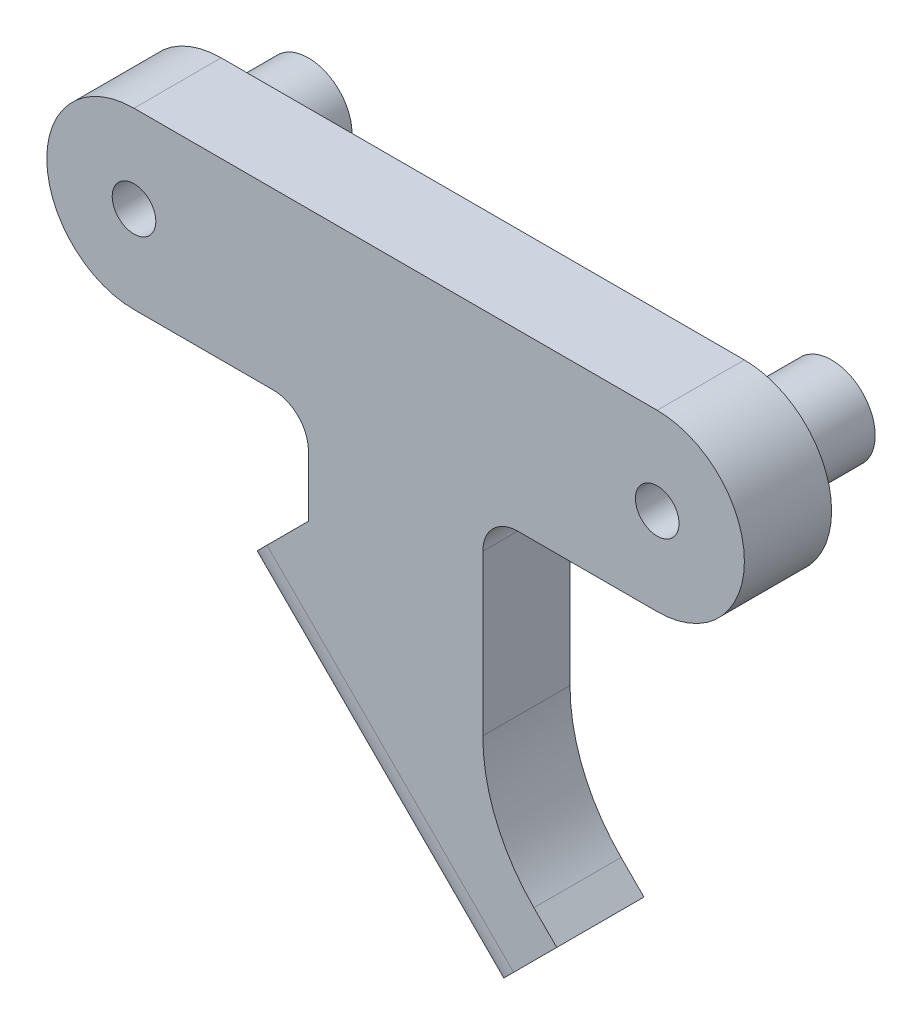
SolidWorks part; units mm, degrees
ref_plane "Piano frontale" through (0, 0, 0) normal (0, 0, 1) x (1, 0, 0)
ref_plane "Piano superiore" through (0, 0, 0) normal (0, 1, 0) x (1, 0, 0)
ref_plane "Piano destro" through (0, 0, 0) normal (1, 0, 0) x (0, 0, -1)
sketch "Schizzo1" plane through (0, 0, 0) normal (0, 0, 1) x (1, 0, 0)
  line L1 (-13.208, 5) -> (16.792, 5)
  line L2 (-13.208, -5) -> (-3.208, -5)
  line L3 (6.792, -28.7941) -> (6.792, -18.7941)
  line L4 (-3.208, -18.7941) -> (6.792, -28.7941)
  line L5 (6.792, -5) -> (16.792, -5)
  line L7 (-3.208, -5) -> (-3.208, -18.7941)
  line L9 (6.792, -5) -> (6.792, -18.7941)
  line L10 (6.792, 0) -> (16.792, 0) construction
  arc A0 (-13.208, 5) -> (-13.208, -5) centre (-13.208, 0) ccw
  arc A1 (16.792, -5) -> (16.792, 5) centre (16.792, 0) ccw
  point P3 (1.792, 0)
  dimension "D1" = 30
  dimension "D2" = 10
  dimension "D3" = 10
  dimension "D4" = 10
extrude "Estrusione-Estrusione3" add sketch "Schizzo1" along normal blind 5 contours L2 L7 L4 L3 L9 L5 A1 L1 A0
sketch "Schizzo3" plane through (0, 0, 0) normal (0, 0, -1) x (-1, 0, 0)
  line L6 (13.208, 5) -> (-16.792, 5)
  line L7 (-16.792, -5) -> (-6.792, -5)
  line L8 (-6.792, -5) -> (-6.792, -28.7941)
  line L9 (-6.792, -28.7941) -> (3.208, -18.7941)
  line L10 (3.208, -18.7941) -> (3.208, -5)
  line L11 (3.208, -5) -> (13.208, -5)
  line L12 (13.208, 5) -> (-16.792, 5) construction
  line L13 (-16.792, -5) -> (-6.792, -5) construction
  line L14 (-6.792, -5) -> (-6.792, -28.7941) construction
  line L15 (-6.792, -28.7941) -> (3.208, -18.7941) construction
  line L16 (3.208, -18.7941) -> (3.208, -5) construction
  line L17 (3.208, -5) -> (13.208, -5) construction
  circle A0 centre (-16.792, 0) radius 2.5
  circle A1 centre (13.208, 0) radius 2.5
  arc A2 (13.208, -5) -> (13.208, 5) centre (13.208, 0) ccw
  arc A3 (-16.792, 5) -> (-16.792, -5) centre (-16.792, 0) ccw
  arc A4 (13.208, -5) -> (13.208, 5) centre (13.208, 0) ccw construction
  arc A5 (-16.792, 5) -> (-16.792, -5) centre (-16.792, 0) ccw construction
  dimension "D1" = 0
extrude "Estrusione-Estrusione4" add sketch "Schizzo3" along normal blind 5
ref_plane "Piano1" through (17.7931, -17.7931, 0) normal (-0.7071, 0.7071, 0) x (0, 0, -1)
sketch "Schizzo7" plane through (17.7931, -17.7931, 0) normal (-0.7071, 0.7071, 0) x (0, 0, -1)
  line L0 (-5, 15.5578) -> (-5, -1.2671) construction
  line L1 (0, 15.5578) -> (-5, 15.5578)
  line L2 (0, 15.5578) -> (0, 9.5578)
  line L3 (0, 9.5578) -> (-5, 9.5578)
  line L4 (-5, 15.5578) -> (-5, 9.5578)
  dimension "D1" = 6
extrude "Estrusione-Estrusione5" add sketch "Schizzo7" along normal blind 20
sketch "Schizzo6" plane through (17.7931, -17.7931, 0) normal (-0.7071, 0.7071, 0) x (0, 0, -1)
  line L0 (0, -1.2671) -> (0, 9.5578) construction
  line L1 (-5, 15.5578) -> (0, 15.5578) construction
  circle A0 centre (-2.5, 12.5578) radius 1.65
  dimension "D1" = 3.3
  dimension "D2" = 2.5
  dimension "D3" = 3
extrude "Taglio-Estrusione1" cut sketch "Schizzo6" along normal up to surface (20 mm away) up to face at (-5.2791, -12.5809, 2.5)
fillet "Raccordo1" radius 2.5 2 edges at (-0.2791, -21.723, 0) (-0.2791, -21.723, 5)
sketch "Schizzo8" plane through (0, 0, -5) normal (0, 0, -1) x (-1, 0, 0)
  circle A0 centre (-16.792, 0) radius 1.25
  circle A1 centre (13.208, 0) radius 1.25
  dimension "D1" = 2.5
extrude "Taglio-Estrusione2" cut sketch "Schizzo8" against normal through all
fillet "Raccordo2" radius 2 2 edges at (-3.208, -5, 2.5) (6.792, -5, 2.5)
fillet "Raccordo3" radius 10 1 edges at (6.792, -20.3088, 2.5)
